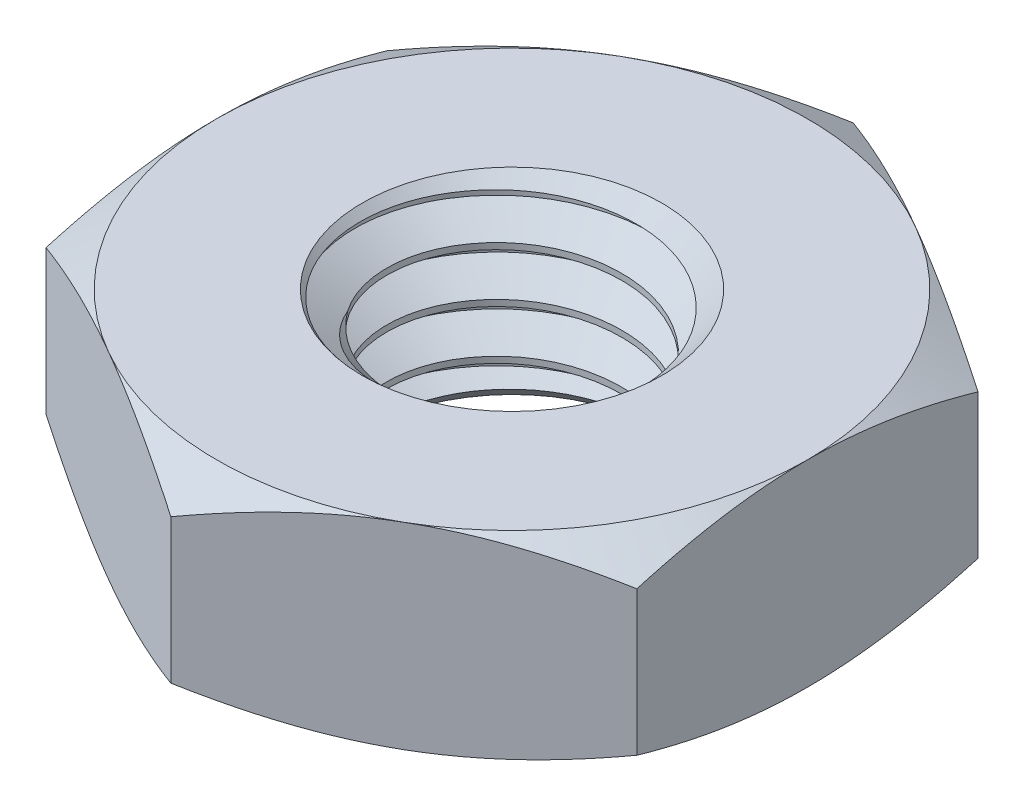
SolidWorks part; units mm, degrees
ref_plane "Front Plane" through (0, 0, 0) normal (0, 0, 1) x (1, 0, 0)
ref_plane "Top Plane" through (0, 0, 0) normal (0, 1, 0) x (1, 0, 0)
ref_plane "Right Plane" through (0, 0, 0) normal (1, 0, 0) x (0, 0, -1)
sketch "Sketch7" plane through (0, 0, 0) normal (0, 1, 0) x (1, 0, 0)
  line L0 (-4.7625, 0) -> (4.7625, 0) construction
  line L1 (-2.413, 0) -> (2.413, 0) construction
  line L2 (-4.7625, 0) -> (-4.7625, -0.7937) construction
  point P4 (0, 0)
  point P8 (0, 0)
sketch "Sketch6" plane through (0, 0, 0) normal (1, 0, 0) x (0, 0, -1)
  line L0 (0, 1.5875) -> (0, -1.5875) construction
  point P4 (0, 0)
sketch "Sketch1" plane through (0, 0, 0) normal (0, 1, 0) x (1, 0, 0)
  line L1 (-4.7625, 2.7496) -> (-4.7625, -2.7496)
  line L2 (-4.7625, -2.7496) -> (0, -5.4993)
  line L3 (0, -5.4993) -> (4.7625, -2.7496)
  line L4 (4.7625, -2.7496) -> (4.7625, 2.7496)
  line L5 (4.7625, 2.7496) -> (0, 5.4993)
  line L6 (0, 5.4993) -> (-4.7625, 2.7496)
  circle A0 centre (0, 0) radius 4.7625 construction
  circle A1 centre (0, 0) radius 2.413
extrude "Boss-Extrude1" add sketch "Sketch1" along normal mid plane 3.175
sketch "Sketch5" plane through (0, 1.5875, 0) normal (0, 1, 0) x (1, 0, 0)
  circle A0 centre (0, 0) radius 4.7625 construction
  circle A1 centre (0, 0) radius 4.7625
extrude "Cut-Extrude2" cut sketch "Sketch5" against normal through all draft 60 flip side to cut
mirror "Mirror1" about plane through (0, 0, 0) normal (0, 1, 0) of "Cut-Extrude2"
sketch "Sketch14" plane through (0, 1.5875, 0) normal (0, 1, 0) x (1, 0, 0)
  line L0 (-2.413, 0) -> (2.413, 0) construction
  line L1 (0, 2.413) -> (0, -2.413) construction
  circle A0 centre (0, 0) radius 2.413 construction
  point P7 (0, 0)
  point P11 (0, 0)
  point P12 (0, -2.413)
  point P13 (-2.413, 0)
  point P14 (0, 2.413)
  point P15 (2.413, 0)
sketch "Sketch8" plane through (0, 1.5875, 0) normal (0, 1, 0) x (1, 0, 0)
  circle A0 centre (0, 0) radius 2.413 construction
  circle A1 centre (0, 0) radius 2.413
extrude "Boss-Extrude2" add sketch "Sketch8" against normal up to surface (3.175 mm away) separate body up to face at (0, -1.5875, 0)
sketch "Sketch9" plane through (0, 1.5875, 0) normal (0, 1, 0) x (1, 0, 0)
  circle A0 centre (0, 0) radius 2.413 construction
  circle A1 centre (0, 0) radius 2.413
extrude "Boss-Extrude3" add sketch "Sketch9" against normal up to surface (3.175 mm away) up to face at (0, -1.5875, 0)
sketch "Sketch10" plane through (0, 1.5875, 0) normal (0, 1, 0) x (1, 0, 0)
  circle A0 centre (0, 0) radius 2.413 construction
  circle A1 centre (0, 0) radius 2.413
curve "Helix/Spiral1" pitch 0.7937 height 3.9688 radius 2.413 centre (0, 1.5875, 0) axis (0, -1, 0) start towards (0, 0, 1)
sketch "Sketch11" plane through (0, 0, 0) normal (1, 0, 0) x (0, 0, -1)
  line L0 (-2.413, 1.5875) -> (-2.413, 2.282)
  line L1 (2.413, 1.5875) -> (-2.413, 1.5875) construction
  line L2 (-2.413, 2.282) -> (-1.8974, 1.9844)
  line L3 (-1.8974, 1.9844) -> (-1.8974, 1.8852)
  line L4 (-1.8974, 1.8852) -> (-2.413, 1.5875)
  line L5 (-2.413, 1.9348) -> (-1.8974, 1.9348) construction
  line L6 (-2.1552, 2.1332) -> (-2.1552, 1.7363) construction
  spline S0 degree 3 poles (-2.413, 1.5875) (-2.413, 1.5711) (-2.2874, 1.5378) (-1.7507, 1.4883) (-0.9475, 1.4387) (0, 1.3891) (0.9475, 1.3395) (1.7507, 1.2898) (2.2874, 1.2402) (2.4758, 1.1906) (2.2874, 1.141) (1.7507, 1.0914) (0.9475, 1.0418) (0, 0.9922) (-0.9475, 0.9426) (-1.7507, 0.893) (-2.2874, 0.8434) (-2.4758, 0.7938) (-2.2874, 0.7441) (-1.7507, 0.6945) (-0.9475, 0.6449) (0, 0.5953) (0.9475, 0.5457) (1.7507, 0.4961) (2.2874, 0.4465) (2.4758, 0.3969) (2.2874, 0.3473) (1.7507, 0.2977) (0.9475, 0.248) (0, 0.1984) (-0.9475, 0.1488) (-1.7507, 0.0992) (-2.2874, 0.0496) (-2.4758, 0) (-2.2874, -0.0496) (-1.7507, -0.0992) (-0.9475, -0.1488) (0, -0.1984) (0.9475, -0.248) (1.7507, -0.2977) (2.2874, -0.3473) (2.4758, -0.3969) (2.2874, -0.4465) (1.7507, -0.4961) (0.9475, -0.5457) (0, -0.5953) (-0.9475, -0.6449) (-1.7507, -0.6945) (-2.2874, -0.7441) (-2.4758, -0.7938) (-2.2874, -0.8434) (-1.7507, -0.893) (-0.9475, -0.9426) (0, -0.9922) (0.9475, -1.0418) (1.7507, -1.0914) (2.2874, -1.141) (2.4758, -1.1906) (2.2874, -1.2402) (1.7507, -1.2898) (0.9475, -1.3395) (0, -1.3891) (-0.9475, -1.4387) (-1.7507, -1.4883) (-2.2874, -1.5379) (-2.4758, -1.5875) (-2.2874, -1.6371) (-1.7507, -1.6867) (-0.9475, -1.7363) (0, -1.7859) (0.9475, -1.8355) (1.7507, -1.8852) (2.2874, -1.9348) (2.4758, -1.9844) (2.2874, -2.034) (1.7507, -2.0836) (0.9475, -2.1332) (0, -2.1828) (-0.9475, -2.2324) (-1.7507, -2.282) (-2.2874, -2.3316) (-2.413, -2.3648) (-2.413, -2.3813) knots 0 0 0 0 0.0125 0.025 0.0375 0.05 0.0625 0.075 0.0875 0.1 0.1125 0.125 0.1375 0.15 0.1625 0.175 0.1875 0.2 0.2125 0.225 0.2375 0.25 0.2625 0.275 0.2875 0.3 0.3125 0.325 0.3375 0.35 0.3625 0.375 0.3875 0.4 0.4125 0.425 0.4375 0.45 0.4625 0.475 0.4875 0.5 0.5125 0.525 0.5375 0.55 0.5625 0.575 0.5875 0.6 0.6125 0.625 0.6375 0.65 0.6625 0.675 0.6875 0.7 0.7125 0.725 0.7375 0.75 0.7625 0.775 0.7875 0.8 0.8125 0.825 0.8375 0.85 0.8625 0.875 0.8875 0.9 0.9125 0.925 0.9375 0.95 0.9625 0.975 0.9875 1 1 1 1 construction
  dimension "D1" = 60
  dimension "D2" = 0.0992
  dimension "D3" = 0.3969
sweep "Cut-Sweep1" cut profiles "Sketch11" path "Helix/Spiral1" align with end faces yes
combine bodies "Combine1" operation type subtract main body 107 bodies to subtract 108
sketch "Sketch12" plane through (0, 1.5875, 0) normal (0, 1, 0) x (1, 0, 0)
  circle A1 centre (0, 0) radius 2.413
  circle A2 centre (0, 0) radius 2.413
  dimension "D1" = 0
extrude "Cut-Extrude3" cut sketch "Sketch12" against normal through all draft 45
sketch "Sketch13" plane through (0, -1.5875, 0) normal (0, -1, 0) x (1, 0, 0)
  circle A1 centre (0, 0) radius 2.413
  circle A2 centre (0, 0) radius 2.413
  dimension "D1" = 0
extrude "Cut-Extrude4" cut sketch "Sketch13" against normal through all draft 45
ref_axis "10-32 Nut Axis" through (0, -2.1048, 0) along (0, 1, 0)
equation "\"D3@Helix/Spiral1\"=\"Thickness@Sketch6\"+\"Pitch@Sketch7\""
equation "\"Height@Boss-Extrude1\"=\"Thickness@Sketch6\""
equation "\"D4@Helix/Spiral1\"=\"Pitch@Sketch7\""
equation "\"D2@Sketch11\"=\"Pitch@Sketch7\"*.125"
equation "\"D3@Sketch11\"=\"Pitch@Sketch7\"*.5"
